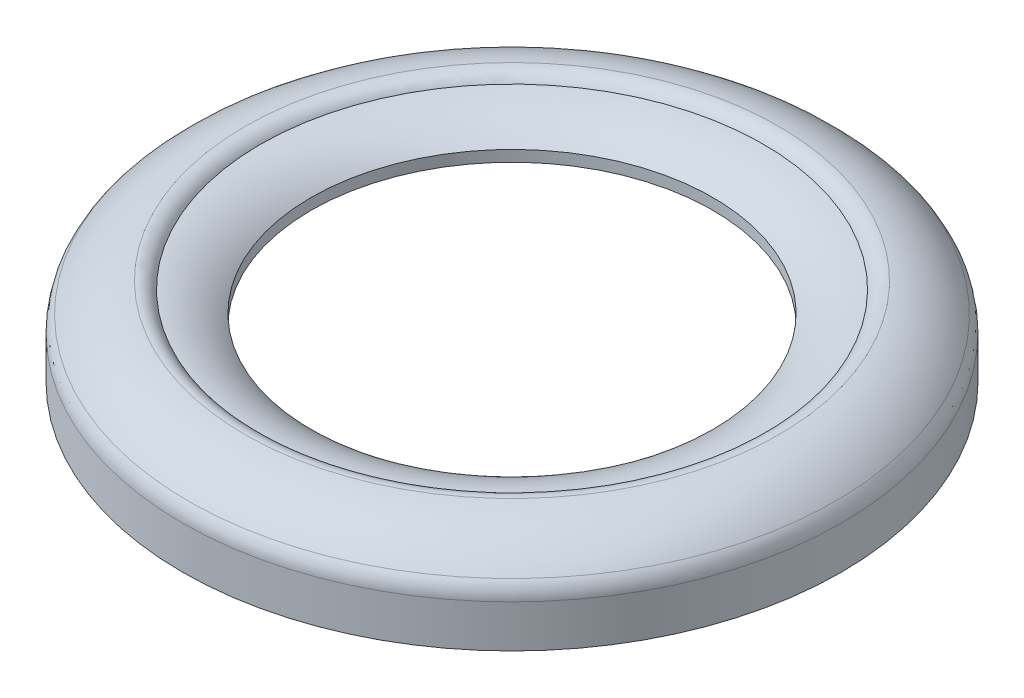
SolidWorks part; units mm, degrees
ref_plane "Спереди" through (0, 0, 0) normal (0, 0, 1) x (1, 0, 0)
ref_plane "Сверху" through (0, 0, 0) normal (0, 1, 0) x (1, 0, 0)
ref_plane "Справа" through (0, 0, 0) normal (1, 0, 0) x (0, 0, -1)
sketch "Эскиз1" plane through (0, 0, 0) normal (0, 0, 1) x (1, 0, 0)
  line L0 (-20, 0) -> (-20, 3)
  line L1 (-16, 5) -> (0, 5) construction
  line L2 (0, 5) -> (0, 0) construction
  line L3 (0, 0) -> (-20, 0) construction
  line L4 (-16, 5) -> (-16, 4.5)
  line L5 (-12.5, 3) -> (-12.5, 0)
  line L6 (-12.5, 0) -> (-20, 0)
  arc A0 (-20, 3) -> (-16, 5) centre (-16, 0) cw
  arc A1 (-16, 4.5) -> (-12.5, 3) centre (-16, -0.3333) cw
  dimension "D1" = 20
  dimension "D2" = 5
  dimension "D3" = 16
  dimension "D4" = 3
  dimension "D5" = 12.5
  dimension "D6" = 0.5
revolve "Повернуть1" add sketch "Эскиз1" angle 360 about L2
fillet "Скругление1" radius 1 1 edges at (-20, 3, 0)
fillet "Скругление2" radius 0.5 1 edges at (-16, 5, 0)
shell "Оболочка1" thickness 0.5 removed face at (-12.5, 3, 0) removed face at (-12.5, 0, 0) outward yes
